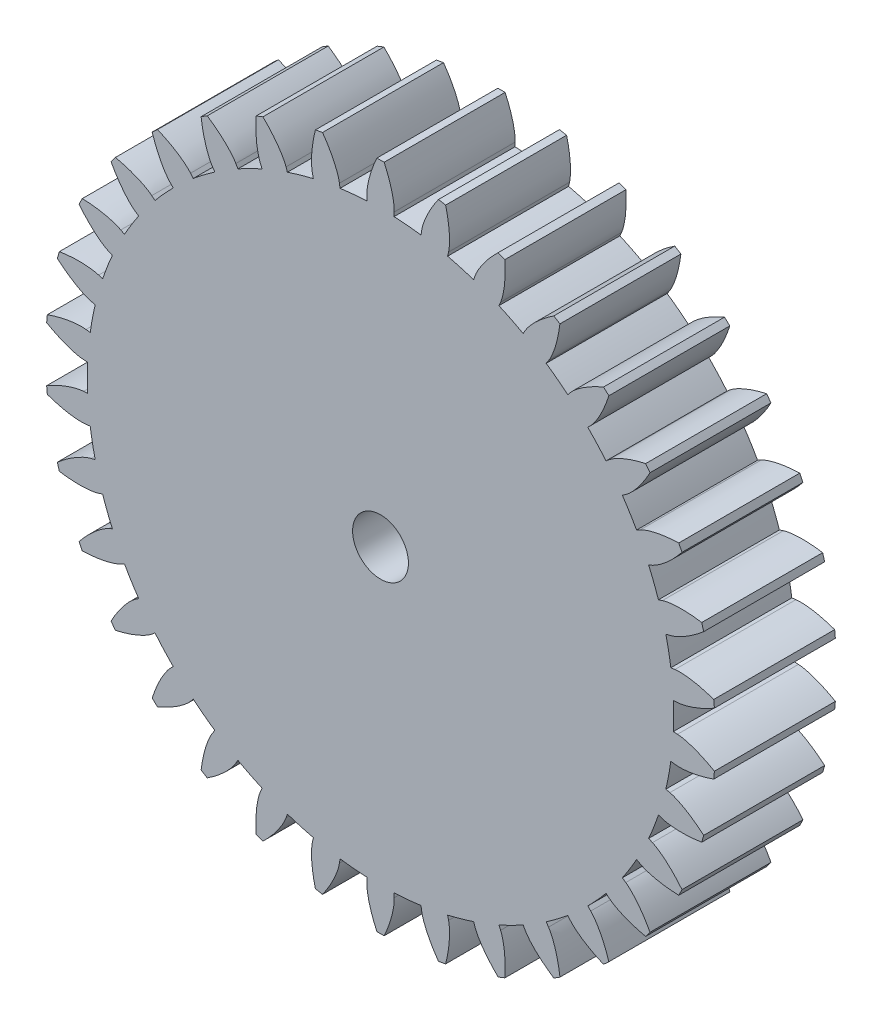
SolidWorks part; units mm, degrees
ref_plane "前视基准面" through (0, 0, 0) normal (0, 0, 1) x (1, 0, 0)
ref_plane "上视基准面" through (0, 0, 0) normal (0, 1, 0) x (1, 0, 0)
ref_plane "右视基准面" through (0, 0, 0) normal (1, 0, 0) x (0, 0, -1)
other "Configuration Table"
sketch "草图1" plane through (0, 0, 0) normal (0, 0, 1) x (1, 0, 0)
  line L0 (0, 0) -> (3, 0) construction
  line L1 (0, 0) -> (2.8978, 0.7765) construction
  line L2 (0, 0) -> (2.7305, 0.701)
  line L3 (2.8978, 0.7765) -> (2.8978, -0.7765) construction
  line L4 (0, 0) -> (2.7305, -0.701)
  circle A0 centre (0, 0) radius 4
  circle A1 centre (0, 0) radius 3 construction
  circle A2 centre (0, 0) radius 1.75
  circle A3 centre (0, 0) radius 2.8191 construction
  circle A4 centre (0, 0) radius 1.5
  spline S0 degree 4 poles (2.7305, 0.701) (2.7514, 0.7063) (2.8083, 0.7255) (2.9105, 0.779) (3.0627, 0.8875) (3.236, 1.0573) (3.4253, 1.3046) (3.6012, 1.6247) (3.742, 2.0003) (3.8364, 2.4221) (3.8779, 2.852) (3.8707, 3.2837) (3.8157, 3.7334) (3.69, 4.2802) (3.4574, 4.9086) (3.0836, 5.5918) (2.5556, 6.2772) (1.9356, 6.8796) (1.2391, 7.3923) (0.4849, 7.8122) (-0.3175, 8.1368) (-1.1468, 8.3674) (-2.0054, 8.5023) (-2.7502, 8.5427) (-3.4127, 8.5171) (-3.8849, 8.4708) (-4.3024, 8.4076) (-4.5772, 8.3558) (-4.9624, 8.2714) (-5.2496, 8.1908) (-5.5362, 8.1071) (-5.6783, 8.056) (-5.7704, 8.0254) knots 0 0 0 0 0 0.005604 0.015718 0.02996 0.048734 0.068727 0.096889 0.125051 0.153212 0.181374 0.209535 0.237696 0.271429 0.327752 0.384075 0.440398 0.496721 0.553044 0.609367 0.66569 0.722013 0.778336 0.834659 0.86282 0.890982 0.909091 0.931818 0.954545 0.977273 1 1 1 1 1 construction
  spline S1 degree 4 poles (2.7305, 0.701) (2.7514, 0.7063) (2.8083, 0.7255) (2.9105, 0.779) (3.0627, 0.8875) (3.236, 1.0573) (3.4253, 1.3046) (3.6012, 1.6247) (3.742, 2.0003) (3.8364, 2.4221) (3.8779, 2.852) (3.8707, 3.2837) (3.8157, 3.7334) (3.69, 4.2802) (3.4574, 4.9086) (3.0836, 5.5918) (2.5556, 6.2772) (1.9356, 6.8796) (1.2391, 7.3923) (0.4849, 7.8122) (-0.3175, 8.1368) (-1.1468, 8.3674) (-2.0054, 8.5023) (-2.7502, 8.5427) (-3.4127, 8.5171) (-3.8849, 8.4708) (-4.2047, 8.4224) (-4.3632, 8.395) (-4.4251, 8.3835) knots 0 0 0 0 0 0.005604 0.015718 0.02996 0.048734 0.068727 0.096889 0.125051 0.153212 0.181374 0.209535 0.237696 0.271429 0.327752 0.384075 0.440398 0.496721 0.553044 0.609367 0.66569 0.722013 0.778336 0.834659 0.86282 0.890982 0.909091 0.909091 0.909091 0.909091 0.909091
  spline S2 degree 4 poles (2.7305, -0.701) (2.7514, -0.7063) (2.8083, -0.7255) (2.9105, -0.779) (3.0627, -0.8875) (3.236, -1.0573) (3.4253, -1.3046) (3.6012, -1.6247) (3.742, -2.0003) (3.8364, -2.4221) (3.8779, -2.852) (3.8707, -3.2837) (3.8157, -3.7334) (3.69, -4.2802) (3.4574, -4.9086) (3.0836, -5.5918) (2.5556, -6.2772) (1.9356, -6.8796) (1.2391, -7.3923) (0.4849, -7.8122) (-0.3175, -8.1368) (-1.1468, -8.3674) (-2.0054, -8.5023) (-2.7502, -8.5427) (-3.4127, -8.5171) (-3.8849, -8.4708) (-4.3024, -8.4076) (-4.5772, -8.3558) (-4.9624, -8.2714) (-5.2496, -8.1908) (-5.5362, -8.1071) (-5.6783, -8.056) (-5.7704, -8.0254) knots 0 0 0 0 0 0.005604 0.015718 0.02996 0.048734 0.068727 0.096889 0.125051 0.153212 0.181374 0.209535 0.237696 0.271429 0.327752 0.384075 0.440398 0.496721 0.553044 0.609367 0.66569 0.722013 0.778336 0.834659 0.86282 0.890982 0.909091 0.931818 0.954545 0.977273 1 1 1 1 1 construction
  spline S3 degree 4 poles (2.7305, -0.701) (2.7514, -0.7063) (2.8083, -0.7255) (2.9105, -0.779) (3.0627, -0.8875) (3.236, -1.0573) (3.4253, -1.3046) (3.6012, -1.6247) (3.742, -2.0003) (3.8364, -2.4221) (3.8779, -2.852) (3.8707, -3.2837) (3.8157, -3.7334) (3.69, -4.2802) (3.4574, -4.9086) (3.0836, -5.5918) (2.5556, -6.2772) (1.9356, -6.8796) (1.2391, -7.3923) (0.4849, -7.8122) (-0.3175, -8.1368) (-1.1468, -8.3674) (-2.0054, -8.5023) (-2.7502, -8.5427) (-3.4127, -8.5171) (-3.8849, -8.4708) (-4.2047, -8.4224) (-4.3632, -8.395) (-4.4251, -8.3835) knots 0 0 0 0 0 0.005604 0.015718 0.02996 0.048734 0.068727 0.096889 0.125051 0.153212 0.181374 0.209535 0.237696 0.271429 0.327752 0.384075 0.440398 0.496721 0.553044 0.609367 0.66569 0.722013 0.778336 0.834659 0.86282 0.890982 0.909091 0.909091 0.909091 0.909091 0.909091
  point P15 (2.8978, 0)
  dimension "齿顶圆直径" = 8
  dimension "分度圆直径" = 6
  dimension "齿根圆直径" = 3.5
  dimension "基圆直径" = 5.6382
  dimension "内孔直径" = 3
  dimension "渐近线镜像线夹角" = 15
extrude "凸台-拉伸1" add sketch "草图1" along normal blind 6 contours A0 | A4
extrude "切除-拉伸1" cut sketch "草图1<3>" along normal through all contours A2 S3 A0 S1 region at (3.0753, 0, 0)
sketch "草图1<3>" plane through (0, 0, 0) normal (0, 0, 1) x (1, 0, 0) same geometry as "草图1"
pattern_circular "阵列(圆周)1" count 6 every 60 about axis through (0, 0, 6) along (0, 0, 1) of "切除-拉伸1"
sketch "草图2" plane through (0, 0, 6) normal (0, 0, 1) x (1, 0, 0)
  line L0 (0, 0) -> (17, 0) construction
  line L1 (0, 0) -> (15.9577, 0.7378)
  line L2 (0, 0) -> (15.9577, -0.7378)
  line L3 (15.9577, 0.7378) -> (15.9577, -0.7378) construction
  circle A0 centre (0, 0) radius 17 construction
  circle A1 centre (0, 0) radius 15.9748 construction
  circle A2 centre (0, 0) radius 15.75
  circle A3 centre (0, 0) radius 18
  circle A4 centre (0, 0) radius 1.5
  spline S0 degree 4 poles (15.9577, -0.7378) (15.9881, -0.7392) (16.0486, -0.7438) (16.1691, -0.7605) (16.3957, -0.8065) (16.6948, -0.8909) (17.2481, -1.094) (18.0858, -1.5149) (19.1293, -2.2277) (20.4292, -3.4225) (21.7265, -5.0346) (22.8823, -6.9919) (23.8246, -9.2524) (24.4799, -11.6107) (24.8647, -14.0271) (25.0011, -16.5907) (24.8383, -19.7656) (24.1599, -23.5015) (22.7461, -27.6823) (20.4768, -32.0278) (17.6078, -35.9999) (14.6524, -39.1038) (11.8542, -41.4763) (9.3704, -43.2539) (7.3013, -44.554) (4.6246, -46.0244) (1.8405, -47.2866) (-1.0281, -48.3386) (-4.552, -49.3492) (-7.2404, -49.9188) (-9.6612, -50.28) (-11.6309, -50.4738) (-12.5542, -50.5441) (-13.4454, -50.5994) (-14.3013, -50.6343) (-15.0594, -50.6573) (-16.1545, -50.6631) (-16.7272, -50.6573) (-17.5581, -50.6392) (-18.226, -50.6121) (-19.0063, -50.5744) (-19.8384, -50.5172) (-20.838, -50.4326) (-21.8068, -50.3295) (-22.7931, -50.2076) (-23.5182, -50.1024) (-24.009, -50.0262) (-24.2505, -49.9866) knots 0 0 0 0 0 0.001401 0.002802 0.005604 0.010661 0.015718 0.02996 0.048734 0.068727 0.096889 0.125051 0.153212 0.181374 0.209535 0.237696 0.271429 0.327752 0.384075 0.440398 0.496721 0.553044 0.581206 0.609367 0.637529 0.66569 0.722013 0.750174 0.778336 0.834659 0.84874 0.86282 0.869861 0.876901 0.890982 0.900036 0.909091 0.920455 0.926136 0.931818 0.943182 0.954545 0.965909 0.977273 0.988636 1 1 1 1 1 construction
  spline S1 degree 4 poles (15.9577, -0.7378) (15.9881, -0.7392) (16.0486, -0.7438) (16.1691, -0.7605) (16.3957, -0.8065) (16.6948, -0.8909) (17.2481, -1.094) (18.0858, -1.5149) (19.1293, -2.2277) (20.4292, -3.4225) (21.7265, -5.0346) (22.8823, -6.9919) (23.8246, -9.2524) (24.4799, -11.6107) (24.8647, -14.0271) (25.0011, -16.5907) (24.8383, -19.7656) (24.1599, -23.5015) (22.7461, -27.6823) (20.4768, -32.0278) (17.6078, -35.9999) (14.6524, -39.1038) (11.8542, -41.4763) (9.3704, -43.2539) (7.3013, -44.554) (4.6246, -46.0244) (1.8405, -47.2866) (-1.0281, -48.3386) (-4.552, -49.3492) (-7.2404, -49.9188) (-9.6612, -50.28) (-11.6309, -50.4738) (-12.5542, -50.5441) (-13.4454, -50.5994) (-14.3013, -50.6343) (-15.0594, -50.6573) (-15.8687, -50.6616) (-16.2256, -50.6607) (-16.404, -50.6592) knots 0 0 0 0 0 0.001401 0.002802 0.005604 0.010661 0.015718 0.02996 0.048734 0.068727 0.096889 0.125051 0.153212 0.181374 0.209535 0.237696 0.271429 0.327752 0.384075 0.440398 0.496721 0.553044 0.581206 0.609367 0.637529 0.66569 0.722013 0.750174 0.778336 0.834659 0.84874 0.86282 0.869861 0.876901 0.890982 0.900036 0.909091 0.909091 0.909091 0.909091 0.909091
  spline S2 degree 4 poles (15.9577, 0.7378) (15.9881, 0.7392) (16.0486, 0.7438) (16.1691, 0.7605) (16.3957, 0.8065) (16.6948, 0.8909) (17.2481, 1.094) (18.0858, 1.5149) (19.1293, 2.2277) (20.4292, 3.4225) (21.7265, 5.0346) (22.8823, 6.9919) (23.8246, 9.2524) (24.4799, 11.6107) (24.8647, 14.0271) (25.0011, 16.5907) (24.8383, 19.7656) (24.1599, 23.5015) (22.7461, 27.6823) (20.4768, 32.0278) (17.6078, 35.9999) (14.6524, 39.1038) (11.8542, 41.4763) (9.3704, 43.2539) (7.3013, 44.554) (4.6246, 46.0244) (1.8405, 47.2866) (-1.0281, 48.3386) (-4.552, 49.3492) (-7.2404, 49.9188) (-9.6612, 50.28) (-11.6309, 50.4738) (-12.5542, 50.5441) (-13.4454, 50.5994) (-14.3013, 50.6343) (-15.0594, 50.6573) (-16.1545, 50.6631) (-16.7272, 50.6573) (-17.5581, 50.6392) (-18.226, 50.6121) (-19.0063, 50.5744) (-19.8384, 50.5172) (-20.838, 50.4326) (-21.8068, 50.3295) (-22.7931, 50.2076) (-23.5182, 50.1024) (-24.009, 50.0262) (-24.2505, 49.9866) knots 0 0 0 0 0 0.001401 0.002802 0.005604 0.010661 0.015718 0.02996 0.048734 0.068727 0.096889 0.125051 0.153212 0.181374 0.209535 0.237696 0.271429 0.327752 0.384075 0.440398 0.496721 0.553044 0.581206 0.609367 0.637529 0.66569 0.722013 0.750174 0.778336 0.834659 0.84874 0.86282 0.869861 0.876901 0.890982 0.900036 0.909091 0.920455 0.926136 0.931818 0.943182 0.954545 0.965909 0.977273 0.988636 1 1 1 1 1 construction
  spline S3 degree 4 poles (15.9577, 0.7378) (15.9881, 0.7392) (16.0486, 0.7438) (16.1691, 0.7605) (16.3957, 0.8065) (16.6948, 0.8909) (17.2481, 1.094) (18.0858, 1.5149) (19.1293, 2.2277) (20.4292, 3.4225) (21.7265, 5.0346) (22.8823, 6.9919) (23.8246, 9.2524) (24.4799, 11.6107) (24.8647, 14.0271) (25.0011, 16.5907) (24.8383, 19.7656) (24.1599, 23.5015) (22.7461, 27.6823) (20.4768, 32.0278) (17.6078, 35.9999) (14.6524, 39.1038) (11.8542, 41.4763) (9.3704, 43.2539) (7.3013, 44.554) (4.6246, 46.0244) (1.8405, 47.2866) (-1.0281, 48.3386) (-4.552, 49.3492) (-7.2404, 49.9188) (-9.6612, 50.28) (-11.6309, 50.4738) (-12.5542, 50.5441) (-13.4454, 50.5994) (-14.3013, 50.6343) (-15.0594, 50.6573) (-15.8687, 50.6616) (-16.2256, 50.6607) (-16.404, 50.6592) knots 0 0 0 0 0 0.001401 0.002802 0.005604 0.010661 0.015718 0.02996 0.048734 0.068727 0.096889 0.125051 0.153212 0.181374 0.209535 0.237696 0.271429 0.327752 0.384075 0.440398 0.496721 0.553044 0.581206 0.609367 0.637529 0.66569 0.722013 0.750174 0.778336 0.834659 0.84874 0.86282 0.869861 0.876901 0.890982 0.900036 0.909091 0.909091 0.909091 0.909091 0.909091
  point P16 (15.9577, 0)
  dimension "内孔直径" = 3
  dimension "分度圆直径" = 34
  dimension "齿顶圆直径" = 36
  dimension "基圆直径" = 31.9495
  dimension "齿根圆直径" = 31.5
  dimension "渐开线镜像线夹角" = 2.647
extrude "凸台-拉伸2" add sketch "草图2" along normal blind 6.5 contours A3 | A4
extrude "切除-拉伸3" cut sketch "草图2<3>" along normal through all contours S3 L1 A2 L2 S1 A3 region at (17.0076, 0, 6)
sketch "草图2<3>" plane through (0, 0, 6) normal (0, 0, 1) x (1, 0, 0) same geometry as "草图2"
pattern_circular "阵列(圆周)2" count 34 over 360 about axis through (0, 0, 12.5) along (0, 0, 1) of "切除-拉伸3"
equation "\"m\"= 1'模数"
equation "\"z\"= 6'齿数"
equation "\"a\"= 20度'压力角"
equation "\"d\"= \"m\" * \"z\"'分度圆直径"
equation "\"da\"= ( \"z\" + 2 ) * \"m\"'齿顶圆直径"
equation "\"df\"= ( \"z\" - 2.5 ) * \"m\"'齿根圆直径"
equation "\"s\"= 0.5 * PI * \"m\"'分度圆齿厚"
equation "\"r\"= 0.38 * \"m\"'齿根圆角"
equation "\"B\"= 0.3 * \"d\"'齿厚"
equation "\"db\"= \"m\" * \"z\" * cos ( \"a\" )'基圆直径"
equation "\"rb\"= \"db\" / 2'基圆半径"
equation "\"齿顶圆直径@草图1\"= \"da\""
equation "\"分度圆直径@草图1\"= \"d\""
equation "\"齿根圆直径@草图1\"= \"df\""
equation "\"基圆直径@草图1\"= \"db\""
equation "\"渐近线镜像线夹角@草图1\"= 360 / 4 / \"z\""
equation "\"h\"= 6'齿轮厚度"
equation "\"ir\"= 3'内孔直径"
equation "\"内孔直径@草图1\"= \"ir\""
equation "\"齿轮厚@凸台-拉伸1\"= \"h\""
equation "\"齿轮夹角@阵列(圆周)1\"= 360 / \"z\""
equation "\"齿数@阵列(圆周)1\"= \"z\""
equation "\"m1\"= 1'模数"
equation "\"z1\"= 34'齿数"
equation "\"a1\"= 20度'压力角"
equation "\"d1\"= \"m1\" * \"z1\"'分度圆直径"
equation "\"da1\"= ( \"z1\" + 2 ) * \"m1\"'齿顶圆直径"
equation "\"df1\"= ( \"z1\" - 2.5 ) * \"m1\"'齿根圆直径"
equation "\"s1\"= 0.5 * PI * \"m1\"'分度圆齿厚"
equation "\"r1\"= 0.38 * \"m1\"'齿根圆角"
equation "\"B1\"= 0.3 * \"d1\"'齿厚"
equation "\"db1\"= \"m1\" * \"z1\" * cos ( \"a1\" )'基圆直径"
equation "\"rb1\"= \"db1\" / 2'基圆半径"
equation "\"分度圆直径@草图2\"= \"d1\""
equation "\"齿顶圆直径@草图2\"= \"da1\""
equation "\"基圆直径@草图2\"= \"db1\""
equation "\"齿根圆直径@草图2\"= \"df1\""
equation "\"渐开线镜像线夹角@草图2\"= 360 / 4 / \"z1\""
equation "\"内孔直径@草图2\"= \"ir\""
equation "\"二层齿轮厚@凸台-拉伸2\" = \"h1\""
equation "\"h1\"= 6.5'齿轮厚度"
equation "\"二层齿数@阵列(圆周)2\"= \"z1\""
